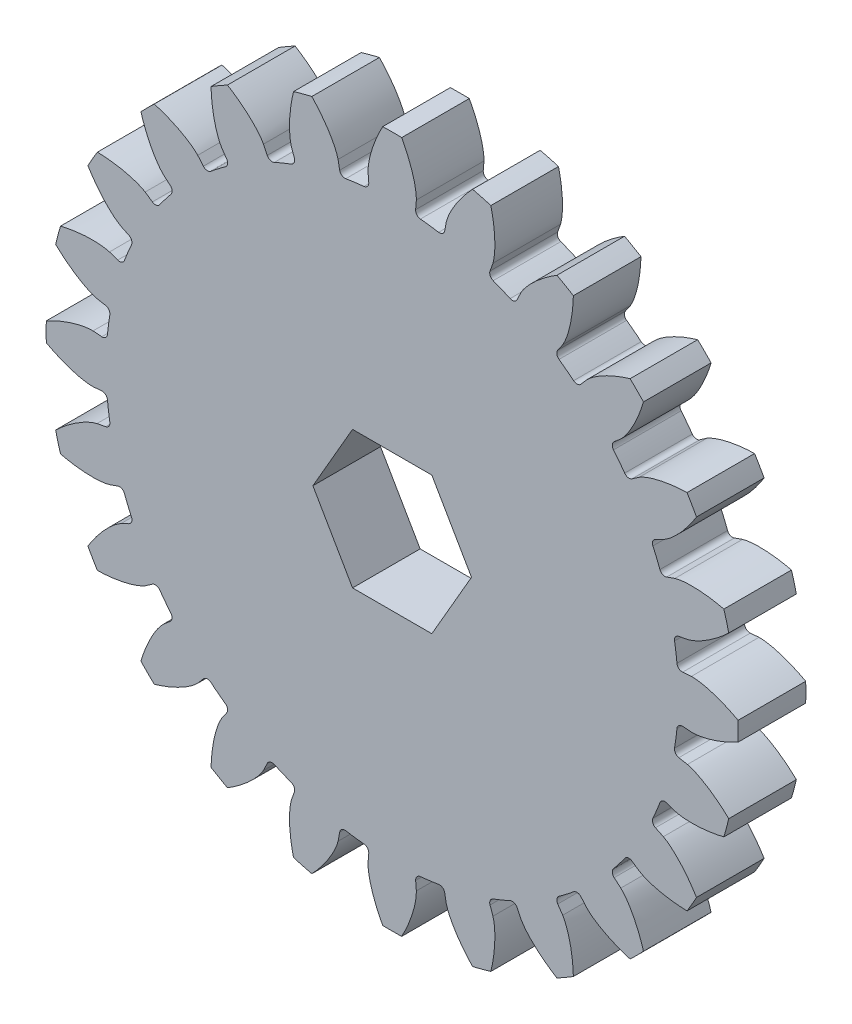
SolidWorks part; units mm, degrees
ref_plane "Front Plane" through (0, 0, 0) normal (0, 0, 1) x (1, 0, 0)
ref_plane "Top Plane" through (0, 0, 0) normal (0, 1, 0) x (1, 0, 0)
ref_plane "Right Plane" through (0, 0, 0) normal (1, 0, 0) x (0, 0, -1)
sketch "Sketch2" plane through (0, 0, 0) normal (0, 0, 1) x (1, 0, 0)
  line L0 (0, 0) -> (2.2683, 28.0994) construction
  line L1 (-0.9652, 28.1742) -> (0, 0) construction
  line L2 (-4.186, 27.8783) -> (0, 0) construction
  line L3 (-7.3518, 27.2153) -> (0, 0) construction
  line L4 (-10.4207, 26.1941) -> (0, 0) construction
  line L5 (-13.3524, 24.8281) -> (0, 0) construction
  line L6 (-13.3524, 24.8281) -> (-10.4207, 26.1941) construction
  line L7 (-10.4207, 26.1941) -> (-7.3518, 27.2153) construction
  line L8 (-7.3518, 27.2153) -> (-4.186, 27.8783) construction
  line L9 (-4.186, 27.8783) -> (-0.9652, 28.1742) construction
  line L10 (-0.9652, 28.1742) -> (2.2683, 28.0994) construction
  line L11 (0, 0) -> (0, 32.5)
  line L12 (-0.9652, 28.1742) -> (2.2672, 28.285) construction
  line L13 (-4.186, 27.8783) -> (2.211, 28.8388) construction
  line L14 (-7.3518, 27.2153) -> (2.0156, 29.7457) construction
  line L15 (-10.4207, 26.1941) -> (1.6005, 30.9764) construction
  line L16 (-13.3524, 24.8281) -> (0.8904, 32.4878) construction
  line L17 (0, 30) -> (1.9635, 30) construction
  line L18 (2.2672, 28.285) -> (5.4997, 28.3957) construction
  line L19 (2.211, 28.8388) -> (5.4095, 29.3191) construction
  line L20 (2.0156, 29.7457) -> (5.1381, 30.5892) construction
  line L21 (1.6005, 30.9764) -> (4.6058, 32.172) construction
  line L22 (0.8904, 32.4878) -> (3.739, 34.0197) construction
  line L23 (0, 0) -> (3.5079, 26.6451)
  line L24 (-0.9652, 28.1742) -> (5.4997, 28.3957) construction
  line L25 (-4.186, 27.8783) -> (5.4095, 29.3191) construction
  line L26 (-7.3518, 27.2153) -> (5.1381, 30.5892) construction
  line L27 (-10.4207, 26.1941) -> (4.6058, 32.172) construction
  line L28 (0, 0) -> (5.0817, 27.729) construction
  line L29 (2.2683, 28.0994) -> (2.2023, 27.2817)
  circle A0 centre (0, 0) radius 30 construction
  circle A1 centre (0, 0) radius 26.875 construction
  circle A2 centre (0, 0) radius 32.5 construction
  circle A3 centre (0, 0) radius 28.1908 construction
  arc A4 (0, 30) -> (1.9621, 29.9358) centre (0, 0) cw construction
  arc A5 (0, 32.5) -> (0.8904, 32.4878) centre (0, 0) cw
  arc A6 (2.2023, 27.2817) -> (2.6513, 26.7439) centre (2.7006, 27.2415) ccw
  arc A7 (2.6513, 26.7439) -> (3.5079, 26.6451) centre (0, 0) cw
  spline S0 degree 3 poles (2.2683, 28.0994) (2.2744, 28.347) (2.2172, 28.9028) (1.8822, 30.4149) (1.3551, 31.6167) (0.8904, 32.4878) knots 0 0 0 0 0.160017 0.360015 1 1 1 1
  dimension "PitchDiameter" = 60
  dimension "BaseDiameter" = 56.3816
  dimension "D3" = 0.5
  dimension "Dedendum" = 3.125
  dimension "Addendum" = 2.5
  dimension "D1" = 1.9635
  dimension "D2" = 7.5
extrude "Boss-Extrude1" add sketch "Sketch2" along normal mid plane 6.35
mirror "Mirror1" about plane through (0, 0, 3.175) normal (1, 0, 0) of "Boss-Extrude1"
ref_plane "Plane1" through (0, 0, 0) normal (0.9914, -0.1305, 0) x (0, 0, -1)
pattern_circular "CirPattern1" count 24 over 360 about axis through (0, 0, 3.175) along (0, 0, -1) of "Boss-Extrude1", "Mirror1" reverse direction yes
sketch "Sketch3" plane through (0, 0, 0) normal (0, 0, 1) x (1, 0, 0)
  circle A0 centre (0, 0) radius 15
  dimension "D1" = 30
extrude "Boss-Extrude2" add sketch "Sketch3" along normal through all
sketch "Sketch4" plane through (0, 0, 3.175) normal (0, 0, 1) x (1, 0, 0)
  line L1 (7.4478, 0) -> (3.7239, 6.45)
  line L2 (3.7239, 6.45) -> (-3.7239, 6.45)
  line L3 (-3.7239, 6.45) -> (-7.4478, 0)
  line L4 (-7.4478, 0) -> (-3.7239, -6.45)
  line L5 (-3.7239, -6.45) -> (3.7239, -6.45)
  line L6 (3.7239, -6.45) -> (7.4478, 0)
  circle A0 centre (0, 0) radius 6.45 construction
  dimension "D1" = 12.9
extrude "Cut-Extrude1" cut sketch "Sketch4" against normal through all
equation "\"N\"= 24'Number of Teeth"
equation "\"P\" = 2.5mm'Inverse Diametral Pitch"
equation "\"PitchDiameter@Sketch2\" = \"N\" * \"P\""
equation "\"Dedendum@Sketch2\" = 1.25 * \"P\""
equation "\"Addendum@Sketch2\" = \"P\""
equation "\"C\"= 20deg'Contact Angle"
equation "\"BaseDiameter@Sketch2\" = \"PitchDiameter@Sketch2\" * cos ( \"C\" ) "
equation "\"D1@Sketch2\"=\"P\"*arcsin(1)/2"
equation "\"D1@CirPattern1\"=\"N\""
equation "\"D2@Sketch2\"=180deg/\"N\""
equation "\"F\"= 0.5mm'Fillet Radius"
equation "\"D3@Sketch2\"=\"F\""
equation "\"D1@Sketch3\"=\"N\"*\"P\"/2"
equation "\"H\"= 12.9mm'Hex Shaft Diameter"
equation "\"D1@Sketch4\"=\"H\""
